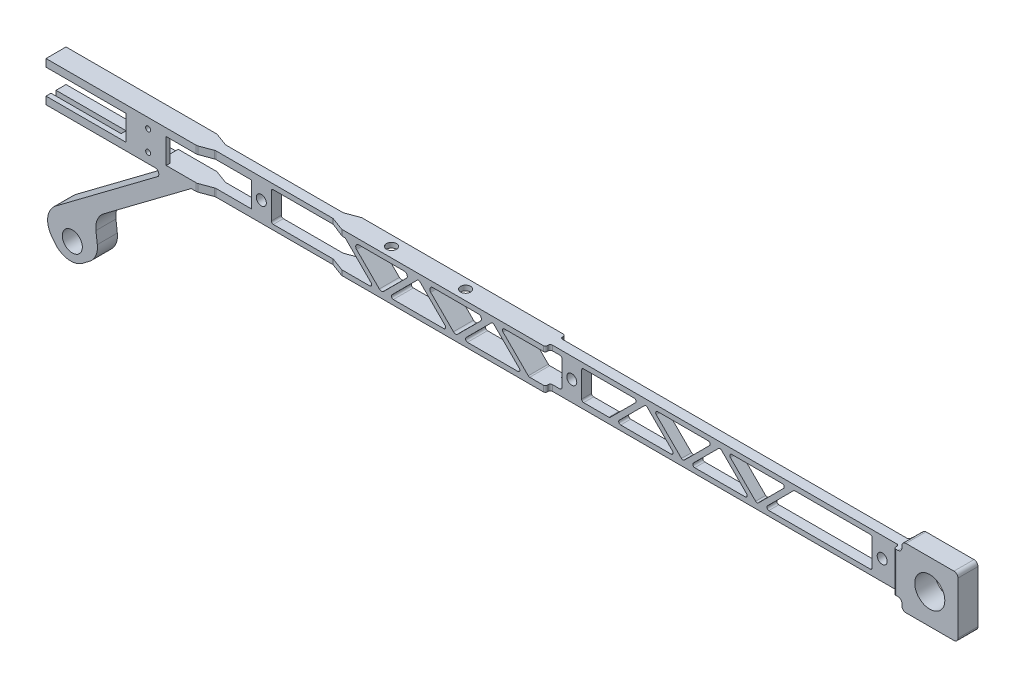
SolidWorks part; units mm, degrees
material "Magnesium Alloy"
ref_plane "Front Plane" through (0, 0, 0) normal (0, 0, 1) x (1, 0, 0)
ref_plane "Top Plane" through (0, 0, 0) normal (0, 1, 0) x (1, 0, 0)
ref_plane "Right Plane" through (0, 0, 0) normal (1, 0, 0) x (0, 0, -1)
sketch "Sketch1" plane through (0, 0, 0) normal (0, 0, 1) x (1, 0, 0)
  line L0 (2.54, 0) -> (568.96, 0)
  line L1 (571.5, 2.54) -> (571.5, 22.86)
  line L2 (568.96, 25.4) -> (2.54, 25.4)
  line L3 (0, 22.86) -> (0, 2.54)
  line L4 (0, 22.86) -> (0, 25.4)
  line L5 (0, 25.4) -> (2.54, 25.4)
  line L6 (0, 2.54) -> (0, 0)
  line L7 (0, 0) -> (2.54, 0)
  arc A1 (568.96, 25.4) -> (571.5, 22.86) centre (568.96, 22.86) cw
  arc A2 (571.5, 2.54) -> (568.96, 0) centre (568.96, 2.54) cw
  point P7 (0, 25.4)
  point P12 (571.5, 0)
  point P15 (0, 0)
  dimension "D3" = 2.54
  dimension "D1" = 571.5
  dimension "D2" = 25.4
extrude "Boss-Extrude1" add sketch "Sketch1" along normal blind 12.7
sketch "Sketch2" plane through (0, 0, 0) normal (0, 0, 1) x (1, 0, 0)
  line L0 (173.2461, 3.175) -> (205.2139, 3.175)
  line L1 (206.112, 5.343) -> (190.128, 21.327)
  line L2 (188.332, 21.327) -> (172.348, 5.343)
  line L3 (0, 0) -> (568.96, 0) construction
  line L4 (0, 25.4) -> (0, 0) construction
  arc A0 (188.332, 21.327) -> (190.128, 21.327) centre (189.23, 20.4289) cw
  arc A1 (206.112, 5.343) -> (205.2139, 3.175) centre (205.2139, 4.445) cw
  arc A2 (173.2461, 3.175) -> (172.348, 5.343) centre (173.2461, 4.445) cw
  point P9 (189.23, 22.225)
  point P12 (208.28, 3.175)
  point P15 (170.18, 3.175)
  dimension "D5" = 1.27
  dimension "D1" = 38.1
  dimension "D2" = 19.05
  dimension "D3" = 3.175
  dimension "D4" = 170.18
extrude "Cut-Extrude1" cut sketch "Sketch2" along normal blind 12.7
pattern_linear "LPattern1" count 7 spacing 46.99 along (1, 0, 0) skipping (3, 0) of "Cut-Extrude1"
sketch "Sketch3" plane through (0, 0, 0) normal (0, 0, 1) x (1, 0, 0)
  line L0 (149.7511, 22.225) -> (181.7189, 22.225)
  line L1 (182.617, 20.057) -> (166.633, 4.073)
  line L2 (164.837, 4.073) -> (148.853, 20.057)
  line L3 (568.96, 25.4) -> (0, 25.4) construction
  line L4 (0, 25.4) -> (0, 0) construction
  arc A0 (164.837, 4.073) -> (166.633, 4.073) centre (165.735, 4.9711) ccw
  arc A1 (182.617, 20.057) -> (181.7189, 22.225) centre (181.7189, 20.955) ccw
  arc A2 (149.7511, 22.225) -> (148.853, 20.057) centre (149.7511, 20.955) ccw
  point P9 (165.735, 3.175)
  point P12 (184.785, 22.225)
  point P15 (146.685, 22.225)
  dimension "D5" = 1.27
  dimension "D1" = 38.1
  dimension "D2" = 19.05
  dimension "D3" = 3.175
  dimension "D4" = 146.685
extrude "Cut-Extrude2" cut sketch "Sketch3" along normal blind 12.7
pattern_linear "LPattern2" count 8 spacing 46.99 along (1, 0, 0) skipping (1, 0), (2, 0) of "Cut-Extrude2"
ref_plane "Plane1" through (279.4, 0, 0) normal (1, 0, 0) x (0, 0, -1)
ref_plane "Plane2" through (330.2, 0, 0) normal (1, 0, 0) x (0, 0, -1)
sketch "Sketch32" plane through (0, 0, 12.7) normal (0, 0, 1) x (1, 0, 0)
  line L0 (198.2741, 22.225) -> (227.1759, 22.225)
  line L1 (228.523, 18.973) -> (214.072, 4.522)
  line L2 (211.378, 4.522) -> (196.927, 18.973)
  line L3 (0, 25.4) -> (0, 0) construction
  line L4 (568.96, 25.4) -> (0, 25.4) construction
  line L5 (206.112, 5.343) -> (190.128, 21.327) construction
  arc A0 (214.072, 4.522) -> (211.378, 4.522) centre (212.725, 5.8691) cw
  arc A1 (227.1759, 22.225) -> (228.523, 18.973) centre (227.1759, 20.32) cw
  arc A2 (198.2741, 22.225) -> (196.927, 18.973) centre (198.2741, 20.32) ccw
  point P13 (231.775, 22.225)
  point P16 (193.675, 22.225)
  dimension "D4" = 1.905
  dimension "D1" = 193.675
  dimension "D2" = 38.1
  dimension "D3" = 3.175
extrude "Cut-Extrude13" cut sketch "Sketch32" against normal up to surface (12.7 mm away) up to face at (380.3287, 12.7, 0)
pattern_linear "LPattern4" count 2 spacing 46.99 along (1, 0, 0) of "Cut-Extrude13"
sketch "Sketch15" plane through (0, 0, 12.7) normal (0, 0, 1) x (1, 0, 0)
  line L0 (0, 20.6375) -> (50.8, 20.6375)
  line L1 (0, 25.4) -> (0, 0) construction
  line L2 (50.8, 20.6375) -> (50.8, 4.7625)
  line L3 (50.8, 4.7625) -> (0, 4.7625)
  line L4 (0, 4.7625) -> (0, 20.6375)
  line L5 (568.96, 25.4) -> (0, 25.4) construction
  dimension "D1" = 15.875
  dimension "D2" = 50.8
  dimension "D3" = 4.7625
extrude "Cut-Extrude6" cut sketch "Sketch15" against normal through all
sketch "Sketch16" plane through (0, 0, 0) normal (-1, 0, 0) x (0, 0, 1)
  line L0 (6.35, 23.8125) -> (9.525, 23.8125)
  line L1 (9.525, 23.8125) -> (9.525, 1.5875)
  line L2 (9.525, 1.5875) -> (6.35, 1.5875)
  line L3 (6.35, 1.5875) -> (6.35, 23.8125)
  line L7 (12.7, 0) -> (0, 0) construction
  line L8 (12.7, 25.4) -> (12.7, 20.6375) construction
  dimension "D1" = 3.175
  dimension "D2" = 3.175
  dimension "D3" = 22.225
  dimension "D4" = 1.5875
extrude "Cut-Extrude7" cut sketch "Sketch16" against normal blind 44.45
sketch "Sketch17" plane through (0, 0, 0) normal (0, 0, 1) x (1, 0, 0)
  line L0 (50.8, 20.6375) -> (54.61, 20.6375)
  line L1 (127, 20.6375) -> (127, 4.7625)
  line L2 (127, 4.7625) -> (71.12, 4.7625)
  line L3 (50.8, 4.7625) -> (50.8, 20.6375)
  line L4 (54.61, 20.6375) -> (55.88, 22.2885)
  line L5 (55.88, 22.2885) -> (71.12, 22.2885)
  line L6 (71.12, 22.2885) -> (71.12, 20.6375)
  line L7 (71.12, 4.7625) -> (71.12, 3.1115)
  line L8 (71.12, 3.1115) -> (55.88, 3.1115)
  line L9 (55.88, 3.1115) -> (54.61, 4.7625)
  line L10 (54.61, 4.7625) -> (50.8, 4.7625)
  line L11 (71.12, 20.6375) -> (127, 20.6375)
  point P15 (52.705, 4.7625)
  dimension "D1" = 76.2
  dimension "D2" = 15.24
  dimension "D3" = 16.51
  dimension "D4" = 1.651
  dimension "D5" = 1.651
  dimension "D6" = 3.81
  dimension "D7" = 3.81
  dimension "D8" = 5.08
extrude "Cut-Extrude8" cut sketch "Sketch17" along normal blind 10.16
sketch "Sketch18" plane through (0, 0, 10.16) normal (0, 0, -1) x (-1, 0, 0)
  line L0 (-127, 4.7625) -> (-76.2, 4.7625)
  line L1 (-71.12, 4.7625) -> (-127, 4.7625) construction
  line L2 (-76.2, 4.7625) -> (-76.2, 20.6375)
  line L3 (-127, 20.6375) -> (-71.12, 20.6375) construction
  line L4 (-76.2, 20.6375) -> (-127, 20.6375)
  line L5 (-127, 20.6375) -> (-127, 4.7625)
  dimension "D1" = 50.8
extrude "Cut-Extrude9" cut sketch "Sketch18" against normal blind 2.54
hole_wizard "1/8 (0.125) Diameter Hole1" positions "Sketch19" profile "Sketch20" hole size "1/8" standard "ANSI Inch" end condition through all
sketch "Sketch19" plane through (0, 0, 10.16) normal (0, 0, -1) x (-1, 0, 0)
  line L0 (-76.2, 4.7625) -> (-76.2, 20.6375) construction
  line L1 (-71.12, 22.2885) -> (-55.88, 22.2885) construction
  line L2 (-55.88, 3.1115) -> (-71.12, 3.1115) construction
  point P0 (-64.77, 19.1135)
  point P2 (-64.77, 6.2865)
  dimension "D1" = 11.43
  dimension "D2" = 3.175
  dimension "D3" = 11.43
  dimension "D4" = 3.175
sketch "Sketch20" plane through (64.77, 19.1135, 10.16) normal (1, 0, 0) x (0, 1, 0)
  line L0 (0, 0) -> (0, 2.54)
  line L1 (0, 2.54) -> (1.5875, 2.54)
  line L2 (1.5875, 2.54) -> (1.5875, 0)
  line L5 (1.5875, 0) -> (0, 0)
  line L11 (0, -6.35) -> (0, 107.95) construction
  dimension "Thru Hole Dia." = 3.175
  dimension "Thru Hole Depth" = 2.54
ref_axis "Axis1" through (189.23, 21.6989, 0) along (0, 0, 1)
sketch "Sketch34" plane through (0, 0, 12.7) normal (0, 0, 1) x (1, 0, 0)
  line L0 (189.23, 21.6989) -> (181.7189, 22.225)
  line L1 (181.7189, 22.225) -> (140.97, 22.225)
  line L2 (139.7, 20.955) -> (139.7, 4.445)
  line L3 (140.97, 3.175) -> (173.2461, 3.175)
  line L4 (173.2461, 3.175) -> (189.23, 21.6989)
  line L5 (127, 20.6375) -> (127, 4.7625) construction
  arc A0 (140.97, 22.225) -> (139.7, 20.955) centre (140.97, 20.955) ccw
  arc A1 (139.7, 4.445) -> (140.97, 3.175) centre (140.97, 4.445) ccw
  dimension "D2" = 1.27
  dimension "D1" = 12.7
extrude "Cut-Extrude14" cut sketch "Sketch34" against normal up to surface (12.7 mm away) up to face at (259.715, 15.297, 0)
sketch "Sketch35" plane through (0, 0, 12.7) normal (0, 0, 1) x (1, 0, 0)
  line L0 (323.9589, 20.955) -> (323.9589, 4.9711)
  line L1 (322.6889, 3.7011) -> (306.705, 3.7011)
  line L2 (306.705, 3.7011) -> (320.1489, 22.225)
  line L3 (322.6889, 22.225) -> (290.7211, 22.225) construction
  line L4 (320.1489, 22.225) -> (322.6889, 22.225)
  arc A1 (305.807, 4.073) -> (307.603, 4.073) centre (306.705, 4.9711) ccw construction
  arc A2 (323.9589, 4.9711) -> (322.6889, 3.7011) centre (322.6889, 4.9711) cw
  arc A3 (322.6889, 22.225) -> (323.9589, 20.955) centre (322.6889, 20.955) cw
  dimension "D1" = 1.27
  dimension "D2" = 2.54
extrude "Cut-Extrude15" cut sketch "Sketch35" against normal up to surface (12.7 mm away) up to face at (171.5874, 14.6574, 0)
mirror "Mirror1" about plane through (330.2, 0, 0) normal (1, 0, 0) of "Cut-Extrude15"
sketch "Sketch8" plane through (0, 0, 0) normal (0, 0, 1) x (1, 0, 0)
  line L0 (92.075, 0) -> (-9.525, -76.2)
  line L1 (0, 0) -> (568.96, 0) construction
  line L2 (-9.525, -76.2) -> (-15.24, -68.58)
  line L3 (-15.24, -68.58) -> (76.2, 0)
  line L4 (76.2, 0) -> (92.075, 0)
  line L6 (0, 4.7625) -> (0, 0) construction
  dimension "D1" = 76.2
  dimension "D2" = 101.6
  dimension "D3" = 9.525
  dimension "D4" = 76.2
extrude "Boss-Extrude3" add sketch "Sketch8" along normal blind 12.7
sketch "Sketch21" plane through (0, 0, 0) normal (0, 0, -1) x (-1, 0, 0)
  line L0 (-76.2, 0) -> (-69.85, 0)
  line L1 (0, 0) -> (-76.2, 0) construction
  line L3 (-76.2, 0) -> (15.24, -68.58) construction
  line L4 (-71.12, -3.81) -> (-76.2, 0)
  arc A0 (-71.12, -3.81) -> (-69.85, 0) centre (-69.0094, -2.3969) cw
  dimension "D1" = 2.54
  dimension "D2" = 6.35
extrude "Boss-Extrude4" add sketch "Sketch21" against normal blind 12.7
sketch "Sketch26" plane through (0, 0, 12.7) normal (0, 0, 1) x (1, 0, 0)
  line L0 (-9.525, -76.2) -> (1.651, -67.818)
  line L1 (-9.525, -76.2) -> (92.075, 0) construction
  line L2 (1.651, -67.818) -> (-0.254, -65.278)
  line L3 (-0.254, -65.278) -> (-11.43, -73.66)
  line L4 (-15.24, -68.58) -> (-9.525, -76.2) construction
  line L5 (-11.43, -73.66) -> (-9.525, -76.2)
  line L6 (71.12, -3.81) -> (-15.24, -68.58) construction
  dimension "D1" = 13.97
  dimension "D2" = 6.35
extrude "Cut-Extrude10" cut sketch "Sketch26" against normal up to surface (12.7 mm away) up to face at (310.7646, 12.7649, 0)
sketch "Sketch28" plane through (0, 0, 12.7) normal (0, 0, 1) x (1, 0, 0)
  line L0 (1.651, -67.818) -> (13.081, -83.058)
  line L1 (13.081, -83.058) -> (33.401, -67.818)
  line L2 (33.401, -67.818) -> (30.7698, -45.9789)
  line L3 (1.651, -67.818) -> (92.075, 0) construction
  line L4 (30.7698, -45.9789) -> (1.651, -67.818)
  circle A0 centre (16.6878, -66.7004) radius 6.35
  dimension "D5" = 12.7
  dimension "D1" = 90
  dimension "D2" = 60
  dimension "D3" = 19.05
  dimension "D4" = 25.4
  dimension "D6" = 8.128
extrude "Boss-Extrude5" add sketch "Sketch28" against normal blind 12.7
sketch "Sketch29" plane through (0, 0, 12.7) normal (0, 0, 1) x (1, 0, 0)
  line L0 (-15.24, -68.58) -> (-11.43, -73.66)
  line L1 (-15.24, -68.58) -> (-4.064, -60.198)
  line L2 (-11.43, -73.66) -> (-0.254, -65.278)
  line L3 (-4.064, -60.198) -> (-0.254, -65.278)
  line L4 (13.081, -83.058) -> (-0.254, -65.278) construction
  dimension "D1" = 0
extrude "Cut-Extrude11" cut sketch "Sketch29" against normal blind 12.7
fillet "Fillet1" radius 12.7 4 edges at (-4.064, -60.198, 6.35) (13.081, -83.058, 6.35) (33.401, -67.818, 6.35) (30.7698, -45.9789, 6.35)
hole_wizard "1/4 (0.25) Diameter Hole1" positions "Sketch22" profile "Sketch23" hole size "1/4" standard "ANSI Inch" end condition through all
sketch "Sketch22" plane through (0, 0, 12.7) normal (0, 0, 1) x (1, 0, 0)
  line L0 (568.96, 25.4) -> (0, 25.4) construction
  line L2 (0, 25.4) -> (0, 20.6375) construction
  point P0 (133.35, 12.7)
  point P2 (330.2, 12.7)
  point P4 (527.05, 12.7)
  dimension "D1" = 12.7
  dimension "D2" = 133.35
  dimension "D3" = 12.7
  dimension "D4" = 196.85
  dimension "D5" = 12.7
  dimension "D6" = 393.7
sketch "Sketch23" plane through (133.35, 12.7, 12.7) normal (1, 0, 0) x (0, -1, 0)
  line L0 (0, 0) -> (0, 12.7)
  line L1 (0, 12.7) -> (3.175, 12.7)
  line L2 (3.175, 12.7) -> (3.175, 0)
  line L5 (3.175, 0) -> (0, 0)
  line L11 (0, -6.35) -> (0, 107.95) construction
  dimension "Thru Hole Dia." = 6.35
  dimension "Thru Hole Depth" = 12.7
hole_wizard "1/4 (0.25) Diameter Hole2" positions "Sketch24" profile "Sketch25" hole size "1/4" standard "ANSI Inch"
sketch "Sketch24" plane through (0, 25.4, 0) normal (0, 1, 0) x (1, 0, 0)
  line L0 (568.96, 0) -> (0, 0) construction
  line L1 (568.96, -12.7) -> (0, -12.7) construction
  line L6 (227.1759, 0) -> (227.1759, -12.7) construction
  line L7 (274.1659, 0) -> (274.1659, -12.7) construction
  point P2 (212.725, -6.35)
  point P8 (259.715, -6.35)
  dimension "D1" = 14.4509
  dimension "D2" = 6.35
  dimension "D3" = 14.4509
  dimension "D6" = 6.35
sketch "Sketch25" plane through (212.725, 25.4, 6.35) normal (1, 0, 0) x (0, 0, 1)
  line L0 (0, 0) -> (0, 5.0827)
  line L1 (0, 5.0827) -> (3.175, 3.175)
  line L2 (3.175, 3.175) -> (3.175, 0)
  line L5 (3.175, 0) -> (0, 0)
  line L10 (0, 5.0827) -> (-3.175, 3.175) construction
  line L11 (0, -6.35) -> (0, 107.95) construction
  dimension "Hole Dia." = 6.35
  dimension "Hole Depth" = 3.175
  dimension "Drill Angle" = 118
sketch "Sketch14" plane through (0, 0, 0) normal (0, 0, -1) x (-1, 0, 0)
  line L0 (-571.5, 2.54) -> (-571.5, 22.86) construction
  line L1 (-92.075, 0) -> (-568.96, 0) construction
  circle A0 centre (-560.3875, 12.7) radius 3.175
  dimension "D1" = 6.35
  dimension "D2" = 11.1125
  dimension "D3" = 12.7
extrude "Cut-Extrude5" cut sketch "Sketch14" against normal through all
sketch "Sketch30" plane through (0, 0, 12.7) normal (0, 0, 1) x (1, 0, 0)
  line L0 (571.5, 2.54) -> (571.5, 22.86) construction
  line L1 (578.2629, 12.7) -> (578.2629, 31.75)
  line L2 (578.2629, 31.75) -> (542.7029, 31.75)
  line L3 (542.7029, 31.75) -> (542.7029, 25.4)
  line L4 (542.7029, 25.4) -> (542.7029, 0)
  line L5 (92.075, 0) -> (568.96, 0) construction
  line L6 (578.2629, 12.7) -> (578.2629, -6.35)
  line L7 (578.2629, -6.35) -> (542.7029, -6.35)
  line L8 (542.7029, -6.35) -> (542.7029, 0)
  circle A2 centre (560.3875, 12.7) radius 3.175
  dimension "D1" = 6.35
  dimension "D2" = 19.05
  dimension "D3" = 19.05
  dimension "D4" = 6.35
  dimension "D5" = 35.56
  dimension "D6" = 17.8754
  dimension "D7" = 6.7629
extrude "Boss-Extrude7" add sketch "Sketch30" against normal blind 12.7
sketch "Sketch31" plane through (0, 0, 12.7) normal (0, 0, 1) x (1, 0, 0)
  circle A0 centre (560.3875, 12.7) radius 9.525
  dimension "D1" = 19.05
extrude "Cut-Extrude12" cut sketch "Sketch31" against normal blind 12.7
fillet "Fillet2" radius 2.54 2 edges at (578.2629, -6.35, 6.35) (578.2629, 31.75, 6.35)
fillet "Fillet5" radius 2.54 4 edges at (542.7029, 0, 6.35) (542.7029, -6.35, 6.35) (542.7029, 25.4, 6.35) (542.7029, 31.75, 6.35)
sketch "Sketch36" plane through (0, 0, 12.7) normal (0, 0, 1) x (1, 0, 0)
  line L0 (471.6961, 22.225) -> (519.43, 22.225)
  line L1 (520.7, 20.955) -> (520.7, 4.445)
  line L2 (519.43, 3.175) -> (487.1539, 3.175)
  line L3 (487.1539, 3.175) -> (470.272, 21.327)
  line L4 (470.272, 21.327) -> (470.798, 21.853)
  line L5 (510.6489, 22.225) -> (478.6811, 22.225) construction
  line L6 (470.272, 21.327) -> (454.288, 5.343) construction
  line L7 (330.2, -6.985) -> (330.2, 6.985) construction
  arc A0 (519.43, 3.175) -> (520.7, 4.445) centre (519.43, 4.445) ccw
  arc A1 (520.7, 20.955) -> (519.43, 22.225) centre (519.43, 20.955) ccw
  arc A2 (471.6961, 22.225) -> (470.798, 21.853) centre (471.6961, 20.955) ccw
  dimension "D1" = 1.27
  dimension "D2" = 190.5
extrude "Cut-Extrude16" cut sketch "Sketch36" against normal up to surface (12.7 mm away) up to face at (569.9125, 12.7, 0)
ref_plane "Plane3" through (0, 0, 6.35) normal (0, 0, 1) x (1, 0, 0)
sketch "Sketch37" plane through (0, 25.4, 0) normal (0, 1, 0) x (1, 0, 0)
  line L0 (187.082, -0.1566) -> (179.313, -3.0184)
  line L2 (178.435, -3.175) -> (104.775, -3.175)
  line L3 (103.897, -3.0184) -> (96.128, -0.1566)
  line L5 (95.25, 0) -> (187.96, 0)
  line L6 (540.1629, 0) -> (0, 0) construction
  line L7 (279.4, -6.985) -> (279.4, 6.985) construction
  arc A0 (187.96, 0) -> (187.082, -0.1566) centre (187.96, -2.54) ccw
  arc A1 (179.313, -3.0184) -> (178.435, -3.175) centre (178.435, -0.635) cw
  arc A2 (104.775, -3.175) -> (103.897, -3.0184) centre (104.775, -0.635) cw
  arc A3 (96.128, -0.1566) -> (95.25, 0) centre (95.25, -2.54) ccw
  dimension "D1" = 2.54
  dimension "D2" = 3.175
  dimension "D3" = 91.44
  dimension "D4" = 73.66
  dimension "D5" = 92.71
extrude "Cut-Extrude17" cut sketch "Sketch37" against normal up to surface (25.4 mm away) up to face at (34.925, 0, 6.35)
sketch "Sketch38" plane through (0, 25.4, 0) normal (0, 1, 0) x (1, 0, 0)
  line L0 (537.6229, -1.27) -> (537.6229, -1.905)
  line L1 (540.1629, 0) -> (187.96, 0) construction
  line L2 (536.3529, -3.175) -> (317.9129, -3.175)
  line L3 (316.6429, -1.905) -> (316.6429, -1.27)
  line L4 (315.3729, 0) -> (537.6229, 0)
  line L5 (537.6229, 0) -> (538.8929, 0)
  arc A0 (315.3729, 0) -> (316.6429, -1.27) centre (315.3729, -1.27) cw
  arc A1 (316.6429, -1.905) -> (317.9129, -3.175) centre (317.9129, -1.905) ccw
  arc A2 (537.6229, -1.905) -> (536.3529, -3.175) centre (536.3529, -1.905) cw
  arc A3 (537.6229, -1.27) -> (538.8929, 0) centre (538.8929, -1.27) cw
  point P19 (537.6229, -3.175)
  dimension "D4" = 1.27
  dimension "D1" = 3.175
  dimension "D3" = 222.25
extrude "Cut-Extrude18" cut sketch "Sketch38" against normal up to surface (25.4 mm away) up to face at (34.925, 0, 6.35)
mirror "Mirror2" about plane through (0, 0, 6.35) normal (0, 0, 1) of "Cut-Extrude17", "Cut-Extrude18"
ref_plane "Plane4" through (292.1, 0, 0) normal (1, 0, 0) x (0, 0, -1)
